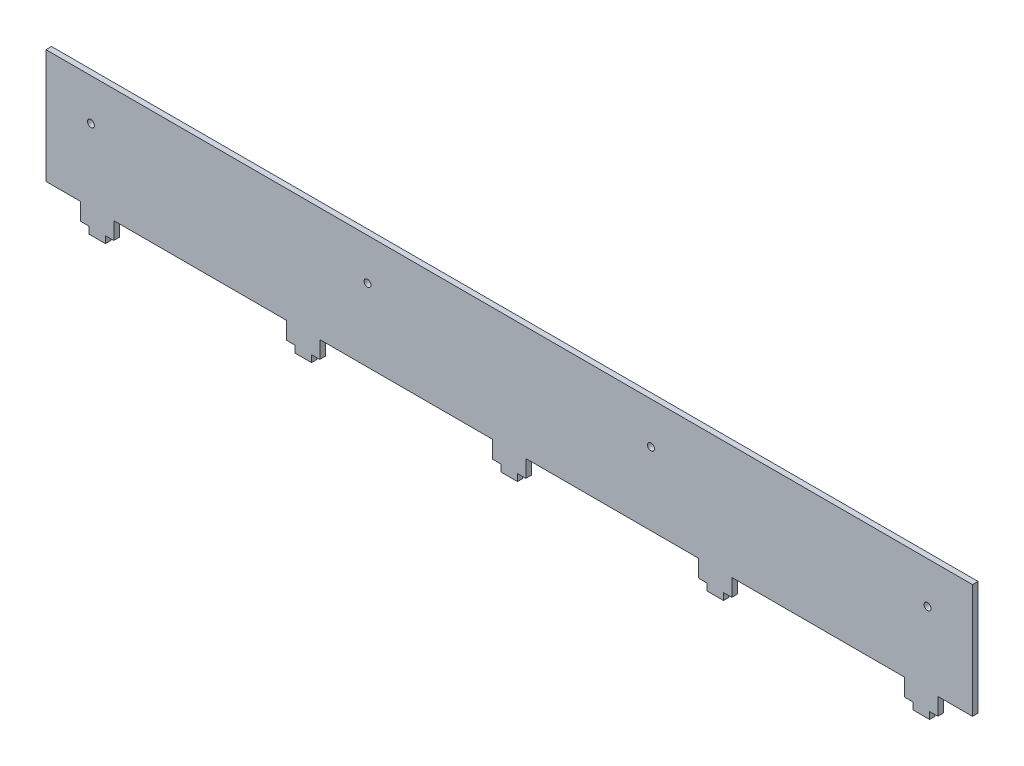
SolidWorks part; units mm, degrees
ref_plane "Спереди" through (0, 0, 0) normal (0, 0, 1) x (1, 0, 0)
ref_plane "Сверху" through (0, 0, 0) normal (0, 1, 0) x (1, 0, 0)
ref_plane "Справа" through (0, 0, 0) normal (1, 0, 0) x (0, 0, -1)
sketch "Эскиз1" plane through (0, 0, 0) normal (0, 0, 1) x (1, 0, 0)
  line L1 (-335, -47.5) -> (335, -47.5)
  line L2 (-335, -47.5) -> (-335, 47.5)
  line L3 (-335, 47.5) -> (335, 47.5)
  line L4 (335, -47.5) -> (335, 47.5)
  line L5 (0, 47.5) -> (0, -47.5) construction
  line L6 (-335, 0) -> (335, 0) construction
  point P0 (0, 0)
  dimension "D1" = 95
  dimension "D2" = 670
extrude "Бобышка-Вытянуть1" add sketch "Эскиз1" along normal mid plane 4
sketch "Эскиз2" plane through (0, 0, 2) normal (0, 0, 1) x (1, 0, 0)
  line L0 (-335, -47.5) -> (335, -47.5) construction
  line L9 (-435, -35.0456) -> (-310, -35.0456)
  line L10 (-435, -35.0456) -> (-435, -47.5)
  line L11 (-435, -47.5) -> (-310, -47.5)
  line L12 (-310, -35.0456) -> (-310, -47.5)
  line L14 (-286, -35.0456) -> (-161, -35.0456)
  line L15 (-286, -35.0456) -> (-286, -47.5)
  line L16 (-286, -47.5) -> (-161, -47.5)
  line L17 (-161, -35.0456) -> (-161, -47.5)
  line L18 (-137, -35.0456) -> (-12, -35.0456)
  line L19 (-137, -35.0456) -> (-137, -47.5)
  line L20 (-137, -47.5) -> (-12, -47.5)
  line L21 (-12, -35.0456) -> (-12, -47.5)
  line L22 (12, -35.0456) -> (137, -35.0456)
  line L23 (12, -35.0456) -> (12, -47.5)
  line L24 (12, -47.5) -> (137, -47.5)
  line L25 (137, -35.0456) -> (137, -47.5)
  line L26 (161, -35.0456) -> (286, -35.0456)
  line L27 (161, -35.0456) -> (161, -47.5)
  line L28 (161, -47.5) -> (286, -47.5)
  line L29 (286, -35.0456) -> (286, -47.5)
  line L30 (310, -35.0456) -> (435, -35.0456)
  line L31 (310, -35.0456) -> (310, -47.5)
  line L32 (310, -47.5) -> (435, -47.5)
  line L33 (435, -35.0456) -> (435, -47.5)
  point P25 (-137, -41.2728)
  point P26 (137, -41.2728)
  dimension "D6" = 125
  dimension "D3" = 125
  dimension "D4" = 125
  dimension "D9" = 125
  dimension "D11" = 125
  dimension "D5" = 24
  dimension "D2" = 24
  dimension "D7" = 24
  dimension "D8" = 24
  dimension "D10" = 24
  dimension "D12" = 125
  dimension "D13" = 12
extrude "Вырез-Вытянуть1" cut sketch "Эскиз2" against normal through all
sketch "Эскиз3" [suppressed] plane through (0, 0, 2) normal (0, 0, 1) x (1, 0, 0)
  line L0 (-328, 5.9544) -> (-328, -6.0456)
  line L1 (-328, -6.0456) -> (-318, -6.0456)
  line L2 (-318, -6.0456) -> (-318, -20.0456)
  line L3 (-318, -20.0456) -> (318, -20.0456)
  line L4 (318, -20.0456) -> (318, -6.0456)
  line L5 (318, -6.0456) -> (328, -6.0456)
  line L6 (328, -6.0456) -> (328, 5.9544)
  line L7 (328, 5.9544) -> (290, 5.9544)
  line L8 (290, 5.9544) -> (280, 35.5)
  line L9 (280, 35.5) -> (240, 35.5)
  line L10 (240, 35.5) -> (230, 5.9544)
  line L11 (230, 5.9544) -> (-230, 5.9544)
  line L12 (-230, 5.9544) -> (-240, 35.5)
  line L13 (-240, 35.5) -> (-280, 35.5)
  line L14 (-280, 35.5) -> (-290, 5.9544)
  line L15 (-290, 5.9544) -> (-328, 5.9544)
  line L16 (0, 0) -> (0, 91.1092) construction
  line L17 (-260, 35.5) -> (-260, 12.7826) construction
  line L18 (260, 35.5) -> (260, 0) construction
  line L19 (-12, -35.0456) -> (-137, -35.0456) construction
  line L20 (-335, 47.5) -> (-335, -35.0456) construction
  line L21 (335, 47.5) -> (-335, 47.5) construction
  dimension "D1" = 15
  dimension "D2" = 14
  dimension "D3" = 12
  dimension "D4" = 60
  dimension "D5" = 38
  dimension "D6" = 7
  dimension "D7" = 17
  dimension "D8" = 12
  dimension "D9" = 40
extrude "Вырез-Вытянуть2" [suppressed] cut sketch "Эскиз3" against normal through all
fillet "Скругление1" [suppressed] radius 10
fillet "Скругление6" [suppressed] radius 2
sketch "Эскиз4" [suppressed] plane through (0, 0, 2) normal (0, 0, 1) x (1, 0, 0)
  circle A1 centre (-302.5, -27.5) radius 2.5
  circle A2 centre (-302.5, -27.5) radius 2.5
  circle A3 centre (0, -27.5) radius 2.5
  circle A4 centre (0, -27.5) radius 2.5
  circle A5 centre (302.5, -27.5) radius 2.5
  circle A6 centre (302.5, -27.5) radius 2.5
  circle A7 centre (-102.5, 17.5) radius 2.5
  circle A8 centre (-102.5, 17.5) radius 2.5
  circle A9 centre (102.5, 17.5) radius 2.5
  circle A10 centre (102.5, 17.5) radius 2.5
  circle A11 centre (-302.5, 17.5) radius 2.5
  circle A12 centre (-302.5, 17.5) radius 2.5
  circle A13 centre (302.5, 17.5) radius 2.5
  circle A14 centre (302.5, 17.5) radius 2.5
  dimension "D1" = 0
  dimension "D2" = 0
  dimension "D3" = 0
  dimension "D4" = 0
  dimension "D5" = 0
  dimension "D6" = 0
  dimension "D7" = 0
extrude "Вырез-Вытянуть3" [suppressed] cut sketch "Эскиз4" against normal through all
sketch "Эскиз5" plane through (0, 0, 2) normal (0, 0, 1) x (1, 0, 0)
  circle A7 centre (-102.5, 17.5) radius 2.5
  circle A8 centre (-102.5, 17.5) radius 2.5
  circle A9 centre (102.5, 17.5) radius 2.5
  circle A10 centre (102.5, 17.5) radius 2.5
  circle A11 centre (-302.5, 17.5) radius 2.5
  circle A12 centre (-302.5, 17.5) radius 2.5
  circle A13 centre (302.5, 17.5) radius 2.5
  circle A14 centre (302.5, 17.5) radius 2.5
  dimension "D4" = 0
  dimension "D5" = 0
  dimension "D6" = 0
  dimension "D7" = 0
extrude "Вырез-Вытянуть4" cut sketch "Эскиз5" against normal through all
sketch "Эскиз6" plane through (0, -47.5, 0) normal (0, -1, 0) x (1, 0, 0)
  line L0 (286, -2) -> (310, -2) construction
  line L2 (310, 2) -> (286, 2) construction
  line L4 (161, 2) -> (137, 2) construction
  line L6 (137, -2) -> (161, -2) construction
  line L8 (-12, -2) -> (12, -2) construction
  line L10 (12, 2) -> (-12, 2) construction
  line L12 (-161, -2) -> (-137, -2) construction
  line L14 (-137, 2) -> (-161, 2) construction
  line L16 (-310, -2) -> (-286, -2) construction
  line L18 (-286, 2) -> (-310, 2) construction
  line L20 (292, -2) -> (304, -2)
  line L21 (304, -2) -> (304, 2)
  line L22 (304, 2) -> (292, 2)
  line L23 (292, 2) -> (292, -2)
  line L24 (155, 2) -> (143, 2)
  line L25 (143, 2) -> (143, -2)
  line L26 (143, -2) -> (155, -2)
  line L27 (155, -2) -> (155, 2)
  line L28 (-6, -2) -> (6, -2)
  line L29 (6, -2) -> (6, 2)
  line L30 (6, 2) -> (-6, 2)
  line L31 (-6, 2) -> (-6, -2)
  line L32 (-155, -2) -> (-143, -2)
  line L33 (-143, -2) -> (-143, 2)
  line L34 (-143, 2) -> (-155, 2)
  line L35 (-155, 2) -> (-155, -2)
  line L36 (-304, -2) -> (-292, -2)
  line L37 (-292, -2) -> (-292, 2)
  line L38 (-292, 2) -> (-304, 2)
  line L39 (-304, 2) -> (-304, -2)
  line L40 (298, 2) -> (298, -2) construction
  line L41 (286, 2) -> (310, 2) construction
  line L42 (149, 2) -> (149, -2) construction
  line L43 (137, 2) -> (161, 2) construction
  line L44 (0, 2) -> (0, -2) construction
  line L45 (-12, 2) -> (12, 2) construction
  line L46 (-149, 2) -> (-149, -2) construction
  line L47 (-161, 2) -> (-137, 2) construction
  line L48 (-298, 2) -> (-298, -2) construction
  line L49 (-310, 2) -> (-286, 2) construction
  point P62 (-292, 0)
  dimension "D1" = 12
  dimension "D2" = 12
  dimension "D3" = 12
  dimension "D4" = 12
  dimension "D5" = 12
extrude "Бобышка-Вытянуть2" add sketch "Эскиз6" along normal blind 5
equation "\"D3@Эскиз2\"=\"D6@Эскиз2\""
equation "\"D4@Эскиз2\"=\"D6@Эскиз2\""
equation "\"D9@Эскиз2\"=\"D6@Эскиз2\""
equation "\"D2@Эскиз2\"=\"D5@Эскиз2\""
equation "\"D7@Эскиз2\"=\"D5@Эскиз2\""
equation "\"D10@Эскиз2\"=\"D5@Эскиз2\""
equation "\"D12@Эскиз2\"=\"D6@Эскиз2\""
equation "\"D13@Эскиз2\"=\"D5@Эскиз2\"/2"
